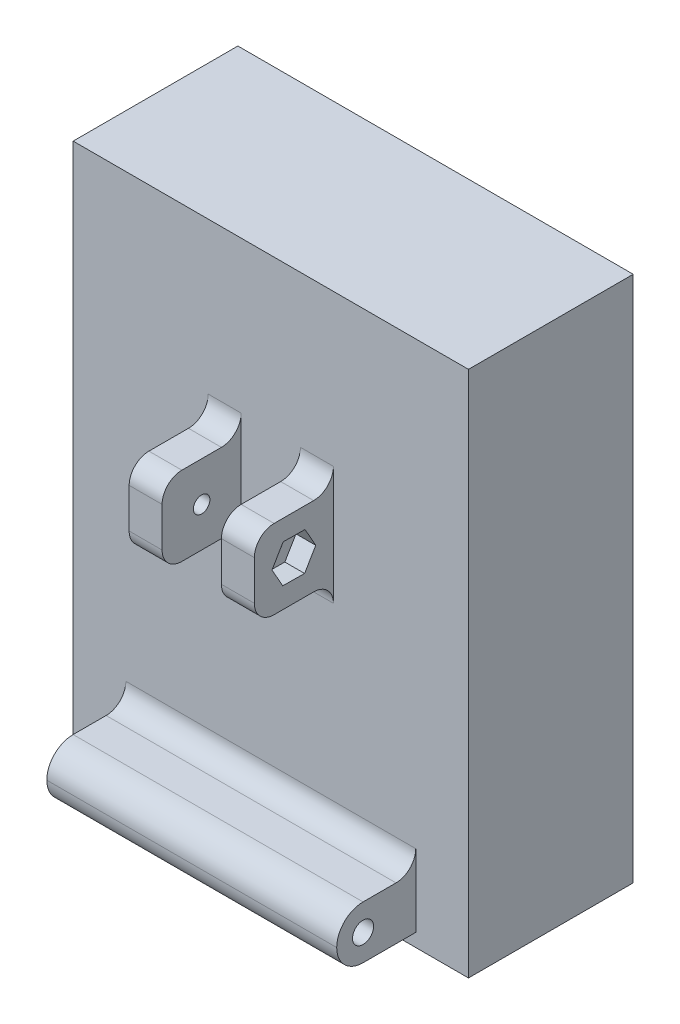
SolidWorks part; units mm, degrees
material "Custom Plastic"
ref_plane "Front Plane" through (0, 0, 0) normal (0, 0, 1) x (1, 0, 0)
ref_plane "Top Plane" through (0, 0, 0) normal (0, 1, 0) x (1, 0, 0)
ref_plane "Right Plane" through (0, 0, 0) normal (1, 0, 0) x (0, 0, -1)
sketch "Sketch1" plane through (0, 0, 0) normal (0, 1, 0) x (1, 0, 0)
  line L1 (-30, -12.5) -> (30, -12.5)
  line L2 (-30, -12.5) -> (-30, 12.5)
  line L3 (-30, 12.5) -> (30, 12.5)
  line L4 (30, -12.5) -> (30, 12.5)
  line L5 (-30, -12.5) -> (30, 12.5) construction
  line L6 (-30, 12.5) -> (30, -12.5) construction
  point P0 (0, 0)
  dimension "D1" = 60
  dimension "D2" = 25
extrude "Boss-Extrude1" add sketch "Sketch1" along normal blind 80 contours L2 L1 L4 L3
sketch "Sketch2" plane through (0, 0, 12.5) normal (0, 0, 1) x (1, 0, 0)
  line L0 (0, 0) -> (0, 6)
  line L1 (0, 6) -> (0, 48)
  line L2 (-22, 10) -> (22, 10)
  line L3 (-22, 10) -> (-22, 2)
  line L4 (-22, 2) -> (22, 2)
  line L5 (22, 10) -> (22, 2)
  line L6 (-22, 10) -> (22, 2) construction
  line L7 (-22, 2) -> (22, 10) construction
  line L8 (0, 48) -> (4.5, 48)
  line L9 (0, 48) -> (-4.5, 48)
  line L10 (-4.5, 48) -> (-4.5, 54)
  line L11 (-4.5, 54) -> (-9.5, 54)
  line L12 (-9.5, 54) -> (-9.5, 42)
  line L13 (-9.5, 42) -> (-4.5, 42)
  line L14 (-4.5, 42) -> (-4.5, 48)
  line L15 (4.5, 48) -> (4.5, 54)
  line L16 (4.5, 54) -> (9.5, 54)
  line L17 (9.5, 54) -> (9.5, 42)
  line L18 (9.5, 42) -> (4.5, 42)
  line L19 (4.5, 42) -> (4.5, 48)
  dimension "D1" = 6
  dimension "D2" = 44
  dimension "D3" = 8
  dimension "D4" = 42
  dimension "D5" = 4.5
  dimension "D6" = 4.5
  dimension "D7" = 5
  dimension "D8" = 12
  dimension "D9" = 6
  dimension "D10" = 5
  dimension "D11" = 12
  dimension "D12" = 6
extrude "Boss-Extrude2" add sketch "Sketch2" along normal blind 12 contours L3 L2 L5 L4 | L10 L11 L12 L13 L14 | L15 L16 L17 L18 L19
sketch "Sketch3" plane through (22, 0, 0) normal (1, 0, 0) x (0, 0, -1)
  line L0 (-24.5, 2) -> (-16.5, 10)
  line L1 (-24.5, 10) -> (-12.5, 10) construction
  circle A0 centre (-20.5, 6) radius 1.6
  dimension "D2" = 3.2
  dimension "D1" = 11.3137
extrude "Cut-Extrude1" cut sketch "Sketch3" against normal through all contours A0
fillet "Fillet1" radius 4 2 edges at (0, 2, 24.5) (0, 10, 24.5)
sketch "Sketch4" plane through (9.5, 0, 0) normal (1, 0, 0) x (0, 0, -1)
  line L0 (-24.5, 54) -> (-12.5, 42)
  circle A0 centre (-18.5, 48) radius 1.25
  dimension "D1" = 2.5
extrude "Cut-Extrude2" cut sketch "Sketch4" against normal through all contours L0 A0 | L0 A0 region at (9.5, 48.3751, 18.1249) region at (9.5, 47.6249, 18.8751)
sketch "Sketch5" plane through (9.5, 0, 0) normal (1, 0, 0) x (0, 0, -1)
  line L1 (-16.8714, 45.1072) -> (-15.1804, 47.964)
  line L2 (-15.1804, 47.964) -> (-16.8091, 50.8568)
  line L3 (-16.8091, 50.8568) -> (-20.1286, 50.8928)
  line L4 (-20.1286, 50.8928) -> (-21.8196, 48.036)
  line L5 (-21.8196, 48.036) -> (-20.1909, 45.1432)
  line L6 (-20.1909, 45.1432) -> (-16.8714, 45.1072)
  circle A0 centre (-18.5, 48) radius 2.875 construction
  dimension "D1" = 5.75
extrude "Cut-Extrude3" cut sketch "Sketch5" against normal blind 3
sketch "Sketch6" plane through (-9.5, 0, 0) normal (-1, 0, 0) x (0, 0, 1)
  circle A0 centre (18.5, 48) radius 3.5
  dimension "D1" = 7
extrude "Cut-Extrude4" cut sketch "Sketch6" against normal blind 3
fillet "Fillet2" radius 3 4 edges at (-7, 42, 24.5) (-7, 54, 24.5) (7, 42, 24.5) (7, 54, 24.5)
fillet "Fillet3" radius 3 5 edges at (7, 54, 12.5) (-7, 54, 12.5) (7, 42, 12.5) (-7, 42, 12.5) (0, 10, 12.5)
